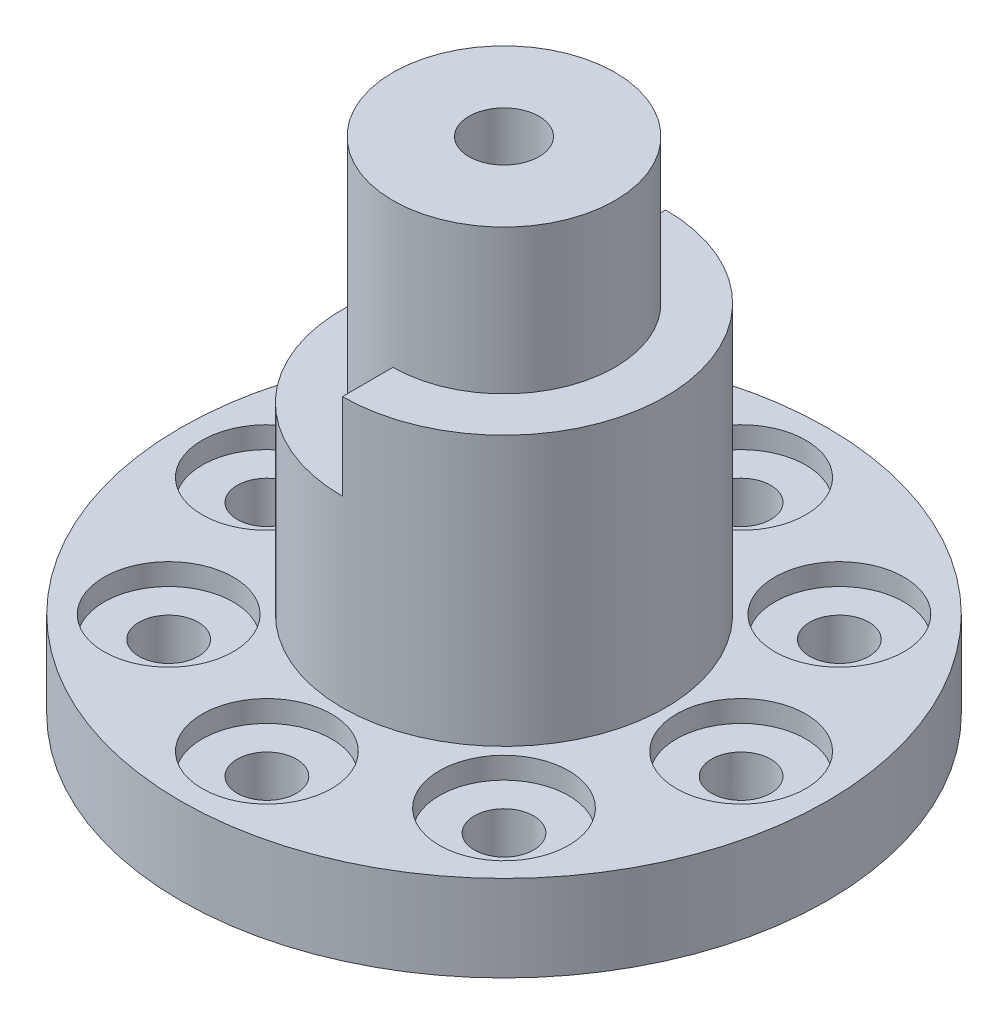
SolidWorks part; units mm, degrees
ref_plane "Front Plane" through (0, 0, 0) normal (0, 0, 1) x (1, 0, 0)
ref_plane "Top Plane" through (0, 0, 0) normal (0, 1, 0) x (1, 0, 0)
ref_plane "Right Plane" through (0, 0, 0) normal (1, 0, 0) x (0, 0, -1)
sketch "Sketch1" plane through (0, 0, 0) normal (0, 1, 0) x (1, 0, 0)
  circle A0 centre (0, 0) radius 7.5
  circle A1 centre (0, 0) radius 5.15
  dimension "D1" = 15
  dimension "D2" = 10.3
extrude "Boss-Extrude1" add sketch "Sketch1" along normal blind 5 contours A1 | A0 A1 region at (-7.2879, 0, 0) region at (0, 0, 0)
extrude "Boss-Extrude2" add sketch "Sketch1<3>" along normal blind 15.7 contours A1 region at (0, 0, 0)
sketch "Sketch1<3>" plane through (0, 0, 0) normal (0, 1, 0) x (1, 0, 0) same geometry as "Sketch1"
sketch "Sketch2" plane through (0, 5, 0) normal (0, 1, 0) x (1, 0, 0)
  line L0 (0, 7.5) -> (0, -7.5)
  circle A0 centre (0, 0) radius 7.5
  circle M2 centre (0, 0) radius 5.15
  circle M3 centre (0, 0) radius 7.5
extrude "Boss-Extrude3" add sketch "Sketch2" along normal blind 4 contours L0 M3 M2 region at (5.1847, 5, -5.1847)
sketch "Sketch3" plane through (0, 0, 0) normal (0, -1, 0) x (1, 0, 0)
  circle A0 centre (0, 0) radius 1.625
  dimension "D1" = 3.25
extrude "Cut-Extrude1" cut sketch "Sketch3" against normal blind 37
sketch "Sketch4" plane through (0, 0, 0) normal (0, -1, 0) x (1, 0, 0)
  circle A0 centre (0, 0) radius 3.5
  dimension "D1" = 7
extrude "Cut-Extrude2" cut sketch "Sketch4" against normal blind 10.7
sketch "Sketch5" plane through (0, 0, 0) normal (0, -1, 0) x (1, 0, 0)
  circle A0 centre (0, 0) radius 3.5
  circle A1 centre (0, 0) radius 7.5
extrude "Boss-Extrude4" add sketch "Sketch5" along normal blind 3.5
sketch "Sketch6" plane through (0, -3.5, 0) normal (0, -1, 0) x (1, 0, 0)
  circle A0 centre (0, 0) radius 3.5
  circle A1 centre (0, 0) radius 11
  circle A2 centre (-11, 0) radius 1.375
  circle A3 centre (-7.7782, 7.7782) radius 1.375
  circle A4 centre (0, 11) radius 1.375
  circle A5 centre (7.7782, 7.7782) radius 1.375
  circle A6 centre (11, 0) radius 1.375
  circle A7 centre (7.7782, -7.7782) radius 1.375
  circle A8 centre (0, -11) radius 1.375
  circle A9 centre (-7.7782, -7.7782) radius 1.375
  circle A10 centre (0, 0) radius 15
  point P22 (0, 0)
  circle M1 centre (0, 0) radius 7.5
  circle M2 centre (0, 0) radius 3.5
  dimension "D1" = 22
  dimension "D2" = 2.75
  dimension "D4" = 30
  dimension "D3" = 8
extrude "Boss-Extrude5" add sketch "Sketch6" along normal blind 4 contours A9 A1 A8 A7 A6 A5 A4 A3 A2 M1 | M1 M2 | A10 A9 A1 A2 A3 A4 A5 A6 A7 A8 region at (9.3163, -3.5, 0) region at (-14.5757, -3.5, 0) region at (-7.2879, -3.5, 0)
sketch "Sketch7" plane through (0, -3.5, 0) normal (0, 1, 0) x (1, 0, 0)
  circle A0 centre (-11, 0) radius 3
  circle A1 centre (-7.7782, 7.7782) radius 3
  circle A2 centre (0, 11) radius 3
  circle A3 centre (7.7782, 7.7782) radius 3
  circle A4 centre (11, 0) radius 3
  circle A5 centre (7.7782, -7.7782) radius 3
  circle A6 centre (0, -11) radius 3
  circle A7 centre (-7.7782, -7.7782) radius 3
  point P19 (0, 0)
  dimension "D1" = 6
  dimension "D2" = 8
extrude "Cut-Extrude3" cut sketch "Sketch7" against normal blind 1
sketch "Sketch8" plane through (0, 9, 0) normal (0, 1, 0) x (1, 0, 0)
  circle A0 centre (0, 0) radius 7.5
  circle A1 centre (0, 0) radius 7.45
  dimension "D1" = 14.9
extrude "Cut-Extrude4" cut sketch "Sketch8" against normal blind 12.5
sketch "Sketch9" plane through (0, 5, 0) normal (0, 1, 0) x (1, 0, 0)
  circle A0 centre (0, 0) radius 7.5
  circle A1 centre (0, 0) radius 7.45
  dimension "D1" = 15
extrude "Boss-Extrude6" add sketch "Sketch9" against normal blind 8.5
sketch "Sketch10" plane through (0, 5, 0) normal (0, 1, 0) x (1, 0, 0)
  line L0 (0, 7.5) -> (0, -7.5)
  circle A0 centre (0, 0) radius 7.5
  circle A1 centre (0, 0) radius 7.45
  arc M2 (0, 7.45) -> (0, -7.45) centre (0, 0) cw
  circle M5 centre (0, 0) radius 7.5
extrude "Boss-Extrude7" add sketch "Sketch10" along normal blind 4 contours L0 M5 M2 region at (5.2914, 5, -5.2914)
